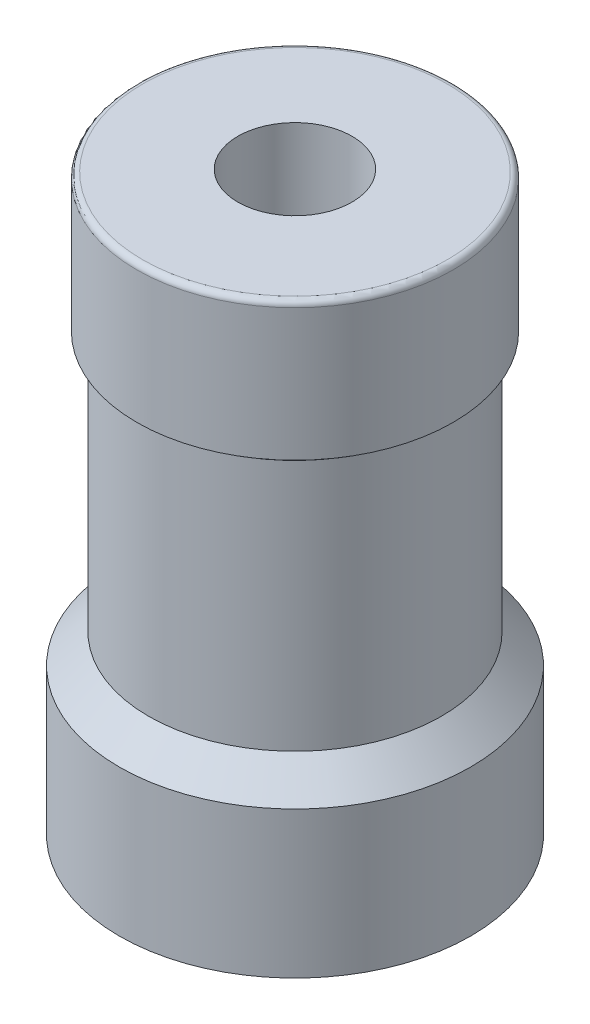
SolidWorks part; units mm, degrees
material "AISI 304"
ref_plane "Front Plane" through (0, 0, 0) normal (0, 0, 1) x (1, 0, 0)
ref_plane "Top Plane" through (0, 0, 0) normal (0, 1, 0) x (1, 0, 0)
ref_plane "Right Plane" through (0, 0, 0) normal (1, 0, 0) x (0, 0, -1)
sketch "Sketch1" plane through (0, 0, 0) normal (1, 0, 0) x (0, 0, -1)
  line L0 (0, 214.3755) -> (0, -63.4147) construction
  line L1 (0, 0) -> (-30, 0)
  line L2 (-30, 0) -> (-30, 30)
  line L3 (-30, 30) -> (-25, 30)
  line L4 (-25, 30) -> (-25, 73)
  line L5 (-25, 73) -> (-27, 74.4503)
  line L6 (-27, 74.4503) -> (-27, 98)
  line L7 (-27, 98) -> (0, 98)
  line L8 (0, 0) -> (0, 98)
  dimension "D1" = 30
  dimension "D2" = 98
  dimension "D3" = 25
  dimension "D4" = 27
  dimension "D5" = 30
  dimension "D6" = 25
revolve "Revolve1" add sketch "Sketch1" angle 360 about L0
hole_wizard "M20x0.5 Tapped Hole1" positions "3DSketch1" profile "Sketch2" tap size "M20x0.5" standard "DIN"
sketch3d "3DSketch1"
  point P0 (-0.4003, 98, -0.3903)
sketch "Sketch2" plane through (-0.4003, 98, -0.3903) normal (1, 0, 0) x (0, 0, 1)
  line L0 (0, 0) -> (0, 59.8584)
  line L1 (0, 59.8584) -> (9.75, 54)
  line L2 (9.75, 54) -> (9.75, 0)
  line L5 (9.75, 0) -> (0, 0)
  line L10 (0, 59.8584) -> (-9.75, 54) construction
  line L11 (0, -6.35) -> (0, 107.95) construction
  dimension "Tap Drill Dia." = 19.5
  dimension "Tap Drill Depth" = 54
  dimension "Drill Angle" = 118
cosmetic thread "Hole Thread1"
chamfer "Chamfer1" distance 5 angle 45 1 edges at (0, 30, 30)
fillet "Fillet3" radius 1 1 edges at (0, 98, 27)
sketch "Sketch3" plane through (0, 0, 0) normal (0, -1, 0) x (1, 0, 0)
  circle A0 centre (0, 0) radius 20 construction
  dimension "D1" = 40
hole_wizard "M6x0.5 Tapped Hole1" positions "3DSketch2" profile "Sketch4" tap size "M6x0.5" standard "DIN"
sketch3d "3DSketch2"
  circle A0 centre (0, 0, 0) radius 20 construction
  point P0 (-0.1258, 0, 19.9996)
  point P4 (0, -20, 0)
sketch "Sketch4" plane through (-0.1258, 0, 19.9996) normal (1, 0, 0) x (0, 0, -1)
  line L0 (0, 0) -> (0, 26.6524)
  line L1 (0, 26.6524) -> (2.75, 25)
  line L2 (2.75, 25) -> (2.75, 0)
  line L5 (2.75, 0) -> (0, 0)
  line L10 (0, 26.6524) -> (-2.75, 25) construction
  line L11 (0, -6.35) -> (0, 107.95) construction
  dimension "Tap Drill Dia." = 5.5
  dimension "Tap Drill Depth" = 25
  dimension "Drill Angle" = 118
cosmetic thread "Hole Thread2"
pattern_circular "CirPattern1" count 3 over 360 about axis through (0.0011, 0, -0.1695) along (0, 1, 0) of "M6x0.5 Tapped Hole1"
cosmetic thread "Hole Thread3"
cosmetic thread "Hole Thread4"
